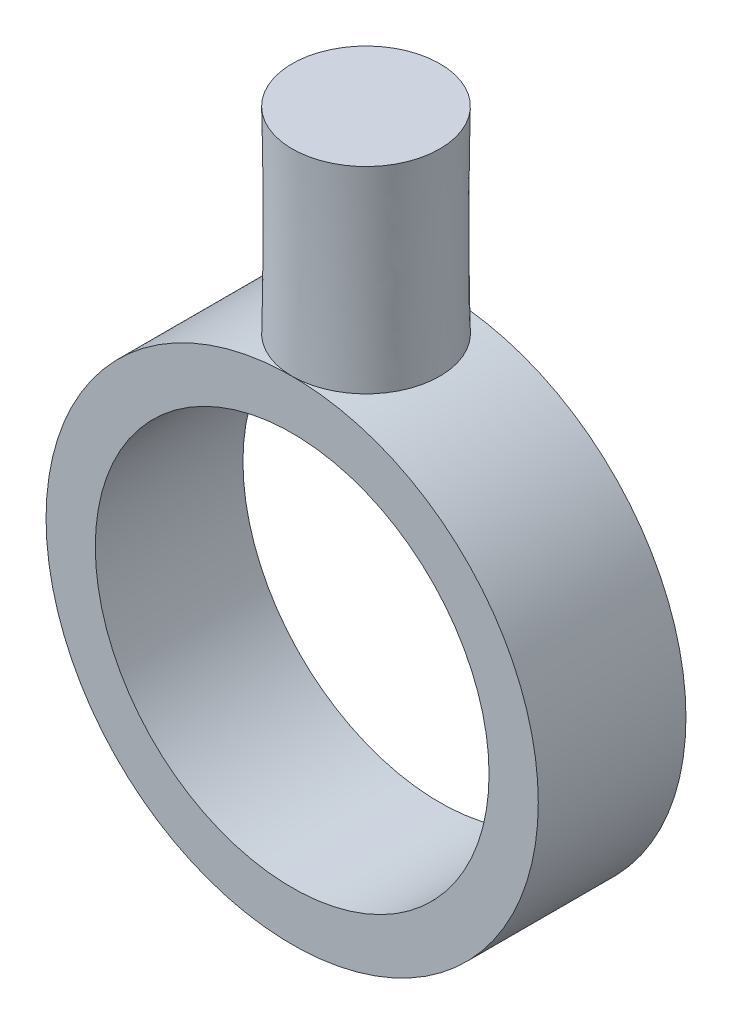
SolidWorks part; units mm, degrees
ref_plane "Front Plane" through (0, 0, 0) normal (0, 0, 1) x (1, 0, 0)
ref_plane "Top Plane" through (0, 0, 0) normal (0, 1, 0) x (1, 0, 0)
ref_plane "Right Plane" through (0, 0, 0) normal (1, 0, 0) x (0, 0, -1)
sketch "Sketch1" plane through (0, 0, 0) normal (0, 0, 1) x (1, 0, 0)
  circle A0 centre (0, 0) radius 40
  circle A1 centre (0, 0) radius 50
  dimension "D1" = 80
  dimension "D2" = 100
extrude "Boss-Extrude1" add sketch "Sketch1" along normal blind 30
ref_plane "Plane1" through (0, 50, 0) normal (0, 1, 0) x (1, 0, 0)
ref_plane "Plane2" through (0, 70, 0) normal (0, 1, 0) x (1, 0, 0)
ref_plane "Plane3" through (0, 90, 0) normal (0, 1, 0) x (1, 0, 0)
sketch "Sketch2" plane through (0, 90, 0) normal (0, 1, 0) x (1, 0, 0)
  line L0 (-55.1158, -14.8243) -> (50, -15) construction
  line L1 (50, -30) -> (50, 0) construction
  line L2 (0, 0) -> (0, -30) construction
  line L3 (50, 0) -> (-50, 0) construction
  line L4 (-50, -30) -> (50, -30) construction
  circle A0 centre (0, -15) radius 15
  dimension "D1" = 30
sketch "Sketch3" plane through (0, 70, 0) normal (0, 1, 0) x (1, 0, 0)
  circle A0 centre (0, -15) radius 15
  dimension "D1" = 30
sketch "Sketch4" plane through (0, 50, 0) normal (0, 1, 0) x (1, 0, 0)
  circle A0 centre (0, -15) radius 15
  dimension "D1" = 30
loft "Loft1" add profiles "Sketch2", "Sketch4" connector at (8.3688, 90, 2.5516) connector at (12.0179, 50, 6.0239)
